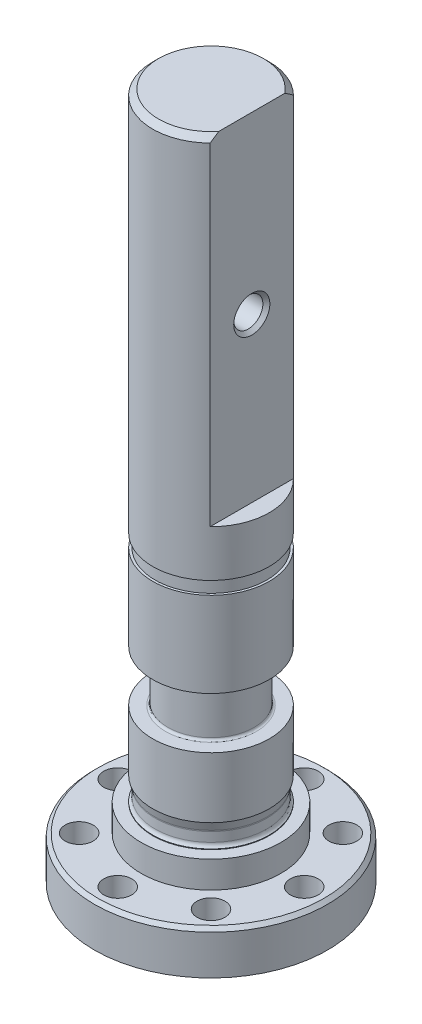
SolidWorks part; units mm, degrees
note: '?' marks a value the reader was unsure of.
material "6063-T6"
ref_plane "Piano frontale" through (0, 0, 0) normal (0, 0, 1) x (1, 0, 0)
ref_plane "Piano superiore" through (0, 0, 0) normal (0, 1, 0) x (1, 0, 0)
ref_plane "Piano destro" through (0, 0, 0) normal (1, 0, 0) x (0, 0, -1)
sketch "Schizzo1" plane through (0, 0, 0) normal (0, 1, 0) x (1, 0, 0)
  circle A0 centre (0, 0) radius 10
  circle A1 centre (0, 8) radius 1.2
  circle A2 centre (5.6569, 5.6569) radius 1.2
  circle A3 centre (8, 0) radius 1.2
  circle A4 centre (5.6569, -5.6569) radius 1.2
  circle A5 centre (0, -8) radius 1.2
  circle A6 centre (-5.6569, -5.6569) radius 1.2
  circle A7 centre (-8, 0) radius 1.2
  circle A8 centre (-5.6569, 5.6569) radius 1.2
  dimension "D1" = 20
  dimension "D2" = 2.4
  dimension "D3" = 8
  dimension "D5" = 8
  dimension "D4" = 8
extrude "Estrusione-Estrusione1" add sketch "Schizzo1" along normal blind 6
sketch "Schizzo2" plane through (0, 6, 0) normal (0, 1, 0) x (1, 0, 0)
  circle A0 centre (0, 0) radius 5
  dimension "D1" = 10
extrude "Estrusione-Estrusione2" add sketch "Schizzo2" along normal blind 53
sketch "Schizzo3" plane through (0, 0, 0) normal (0, 0, 1) x (1, 0, 0)
  line L0 (8, 7.3439) -> (8, -1.7433) construction
  line L1 (10, 6) -> (-10, 6) construction
  line L2 (8, 6) -> (10, 6)
  line L4 (10, 6) -> (8, 4)
  line L5 (8, 4) -> (8, 6)
  dimension "D1" = 8
  dimension "D2" = 45
  dimension "D3" = 2
revolve "Taglia-Rivoluzione1" [suppressed] cut sketch "Schizzo3" angle 360 about L0
pattern_circular "RipetizioneCircolare1" [suppressed] count 8 over 360
sketch "Schizzo9" plane through (0, 0, 0) normal (0, 0, 1) x (1, 0, 0)
  line L0 (0, 0) -> (0, 9.6368) construction
  line L1 (-10, 6) -> (-6, 6)
  line L2 (-10, 6) -> (-10, 3.7)
  line L3 (-10, 3.7) -> (-6, 3.7)
  line L4 (-6, 6) -> (-6, 3.7)
  dimension "D1" = 6
  dimension "D2" = 2.3
revolve "Taglia-Rivoluzione3" cut sketch "Schizzo9" angle 360 about L0
chamfer "Smusso2" [suppressed] distance 0.3 angle 45
chamfer "Smusso3" distance 0.3 angle 45 1 edges at (0, 3.7, -10)
sketch "Schizzo4" plane through (0, 0, 0) normal (0, 0, 1) x (1, 0, 0)
  line L0 (-5.2, 6) -> (-5, 8) construction
  line L1 (-5, 8) -> (-4.8136, 7.3045)
  line L2 (0, 0) -> (0, 10.8887) construction
  line L3 (-5, 59) -> (-5, 6) construction
  line L4 (-4.8, 7.2009) -> (-4.8, 6.4)
  line L5 (-5.2, 6) -> (-7, 6)
  line L6 (5, 6) -> (-5, 6) construction
  line L7 (-5.2, 6) -> (-4.1476, 6) construction
  line L8 (6, 6) -> (-6, 6) construction
  line L9 (-7, 6) -> (-7, 8)
  line L10 (-7, 8) -> (-5, 8)
  arc A0 (-4.8136, 7.3045) -> (-4.8, 7.2009) centre (-5.2, 7.2009) cw
  arc A1 (-4.8, 6.4) -> (-5.2, 6) centre (-5.2, 6.4) cw
  dimension "D1" = 2
  dimension "D2" = 0.4
  dimension "D4" = 0.4
  dimension "D3" = 0.2
  dimension "D5" = 15
  dimension "D6" = 2
revolve "Taglia-Rivoluzione2" cut sketch "Schizzo4" angle 360 about L2
hole_wizard "Foro Ø8.1 (8.1)-1" positions "Schizzo6" profile "Schizzo5" hole size "Ø8.1" standard "ISO"
sketch "Schizzo6" plane through (0, 0, 0) normal (0, -1, 0) x (1, 0, 0)
  circle A0 centre (0, 0) radius 10 construction
  point P0 (0, 0)
sketch "Schizzo5" plane through (0, 0, 0) normal (1, 0, 0) x (0, 0, -1)
  line L0 (0, 0) -> (0, 4.4335)
  line L1 (0, 4.4335) -> (4.05, 2)
  line L2 (4.05, 2) -> (4.05, 0)
  line L5 (4.05, 0) -> (0, 0)
  line L10 (0, 4.4335) -> (-4.05, 2) construction
  line L11 (0, -6.35) -> (0, 107.95) construction
  dimension "Hole Dia." = 8.1
  dimension "Hole Depth" = 2
  dimension "Drill Angle" = 118
chamfer "Smusso5" distance 0.5 angle 45 1 edges at (0, 59, 5)
hole_wizard "Foro Ø5.0 (5)-1" [suppressed] positions "Schizzo8" profile "Schizzo7" hole size "Ø5.0" standard "ISO"
sketch "Schizzo8" plane through (0, 0, 0) normal (0, -1, 0) x (1, 0, 0)
  circle A0 centre (0, 0) radius 10 construction
  point P0 (0, 0)
sketch "Schizzo7" plane through (0, 0, 0) normal (1, 0, 0) x (0, 0, -1)
  line L0 (0, 0) -> (0, 6.0022)
  line L1 (0, 6.0022) -> (2.5, 4.5)
  line L2 (2.5, 4.5) -> (2.5, 0)
  line L5 (2.5, 0) -> (0, 0)
  line L10 (0, 6.0022) -> (-2.5, 4.5) construction
  line L11 (0, -6.35) -> (0, 107.95) construction
  dimension "Hole Dia." = 5
  dimension "Hole Depth" = 4.5
  dimension "Drill Angle" = 118
sketch "Schizzo10" plane through (0, 59, 0) normal (0, 1, 0) x (1, 0, 0)
  line L0 (3.5, -3.5707) -> (3.5, 3.5707)
  circle A0 centre (0, 0) radius 5 construction
  circle A1 centre (0, 0) radius 5 construction
  arc A2 (3.5, -3.5707) -> (3.5, 3.5707) centre (0, 0) ccw
  dimension "D1" = 3.5
extrude "Taglio-Estrusione1" cut sketch "Schizzo10" against normal offset from surface (29 mm away) 24 up to face at (0, 6, -6)
hole_wizard "Preforo da maschiare M3-1" positions "Schizzo12" profile "Schizzo13" hole size "M3" standard "ISO" end condition through all
sketch "Schizzo12" plane through (3.5, 0, 0) normal (1, 0, 0) x (0, 0, -1)
  point P0 (0, 44)
  dimension "D1" = 44
sketch "Schizzo13" plane through (3.5, 44, 0) normal (0, 1, 0) x (0, 0, -1)
  line L0 (0, 0) -> (0, 13.5)
  line L1 (0, 13.5) -> (1.25, 13.5)
  line L2 (1.25, 13.5) -> (1.25, 0)
  line L5 (1.25, 0) -> (0, 0)
  line L11 (0, -6.35) -> (0, 107.95) construction
  dimension "Thru Hole Dia." = 2.5
  dimension "Thru Hole Depth" = 13.5
chamfer "Smusso4" distance 0.3 angle 45 1 edges at (3.5, 44, -1.25)
hole_wizard "Foro Ø8.1 (8.1)-2" positions "Schizzo15" profile "Schizzo14" hole size "Ø8.1" standard "ISO"
sketch "Schizzo15" plane through (0, 0, 0) normal (0, -1, 0) x (1, 0, 0)
  point P0 (0, 0)
sketch "Schizzo14" plane through (0, 0, 0) normal (1, 0, 0) x (0, 0, -1)
  line L0 (0, 0) -> (0, 4.9335)
  line L1 (0, 4.9335) -> (4.05, 2.5)
  line L2 (4.05, 2.5) -> (4.05, 0)
  line L5 (4.05, 0) -> (0, 0)
  line L10 (0, 4.9335) -> (-4.05, 2.5) construction
  line L11 (0, -6.35) -> (0, 107.95) construction
  dimension "Hole Dia." = 8.1
  dimension "Hole Depth" = 2.5
  dimension "Drill Angle" = 118
sketch "Schizzo16" plane through (0, 0, 0) normal (0, 0, 1) x (1, 0, 0)
  line L1 (0, 0) -> (2.35, 0)
  line L2 (0, 0) -> (0, 3.4)
  line L3 (0, 3.4) -> (2.35, 3.4)
  line L4 (2.35, 0) -> (2.35, 3.4)
  dimension "D1" = 3.4
  dimension "D2" = 2.35
ref_axis "Asse1" through (-5, 44, 0) along (1, 0, 0)?
sketch "Schizzo17" plane through (0, 0, 0) normal (0, 0, 1) x (1, 0, 0)
  line L0 (0, 0) -> (0, 42.2172) construction
  line L1 (-5, 11.1) -> (4.9535, 11.1) construction
  line L2 (-5, 42.75) -> (-5, 8) construction
  line L3 (-8.697, 19.1) -> (4.9535, 19.1) construction
  line L4 (-5, 42.75) -> (-5, 8) construction
  line L5 (-5, 17.6) -> (-3.7, 17.6)
  line L6 (-5, 17.6) -> (-5, 13.2)
  line L7 (-5, 13.2) -> (-3.7, 13.2)
  line L8 (-3.7, 17.6) -> (-3.7, 13.2)
  line L9 (-6.8, 3.7) -> (-9.2, 3.7) construction
  dimension "D1" = 7.4
  dimension "D2" = 15.4
  dimension "D3" = 4.4
  dimension "D4" = 1.3
  dimension "D6" = 1.5
revolve "Taglia-Rivoluzione4" cut sketch "Schizzo17" angle 360 about L0
fillet "Raccordo1" radius 0.2 2 edges at (0, 13.2, -3.7) (0, 17.6, -3.7)
sketch "Schizzo18" plane through (0, 0, 0) normal (0, 0, 1) x (1, 0, 0)
  line L0 (-5, 42.75) -> (-5, 17.6) construction
  line L1 (-5, 26) -> (-4.8, 26)
  line L2 (-5, 26) -> (-5, 24.9)
  line L3 (-5, 24.9) -> (-4.8, 24.9)
  line L4 (-4.8, 26) -> (-4.8, 24.9)
  line L5 (9.7, 3.7) -> (-9.7, 3.7) construction
  line L6 (0, 0) -> (0, 33.5598) construction
  dimension "D1" = 22.3
  dimension "D2" = 1.1
  dimension "D3" = 4.8
revolve "Taglia-Rivoluzione5" cut sketch "Schizzo18" angle 360 about L6
